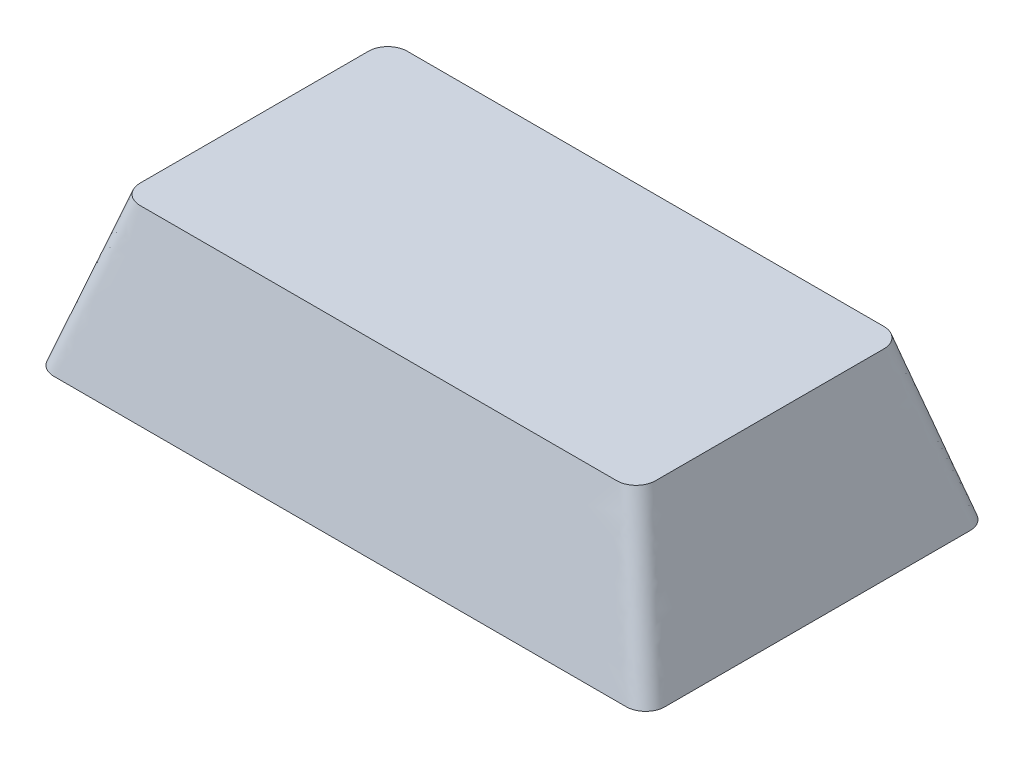
SolidWorks part; units mm, degrees
ref_plane "Alzado" through (0, 0, 0) normal (0, 0, 1) x (1, 0, 0)
ref_plane "Planta" through (0, 0, 0) normal (0, 1, 0) x (1, 0, 0)
ref_plane "Vista lateral" through (0, 0, 0) normal (1, 0, 0) x (0, 0, -1)
sketch "Croquis2" plane through (0, 0, 0) normal (0, 1, 0) x (1, 0, 0)
  line L1 (-14.986, -9.0043) -> (14.986, -9.0043)
  line L2 (-16.002, -7.9883) -> (-16.002, 7.9883)
  line L3 (-14.986, 9.0043) -> (14.986, 9.0043)
  line L4 (16.002, -7.9883) -> (16.002, 7.9883)
  arc A0 (-16.002, 7.9883) -> (-14.986, 9.0043) centre (-14.986, 7.9883) cw
  arc A1 (-14.986, -9.0043) -> (-16.002, -7.9883) centre (-14.986, -7.9883) cw
  arc A2 (14.986, -9.0043) -> (16.002, -7.9883) centre (14.986, -7.9883) ccw
  arc A3 (14.986, 9.0043) -> (16.002, 7.9883) centre (14.986, 7.9883) cw
  point P4 (16.002, 0)
  point P6 (0, 9.0043)
  dimension "D3" = 1.016
  dimension "D1" = 32.004
  dimension "D2" = 18.0086
ref_plane "Plano1" through (0, 8.001, 0) normal (0, 1, 0) x (1, 0, 0)
sketch "Croquis3" plane through (0, 8.001, 0) normal (0, 1, 0) x (1, 0, 0)
  line L1 (-12.4841, -6.9977) -> (12.4841, -6.9977)
  line L2 (-13.5001, -5.9817) -> (-13.5001, 5.9817)
  line L3 (-12.4841, 6.9977) -> (12.4841, 6.9977)
  line L4 (13.5001, -5.9817) -> (13.5001, 5.9817)
  line L5 (-13.5001, -6.9977) -> (13.5001, 6.9977) construction
  line L6 (-13.5001, 6.9977) -> (13.5001, -6.9977) construction
  arc A0 (12.4841, 6.9977) -> (13.5001, 5.9817) centre (12.4841, 5.9817) cw
  arc A1 (12.4841, -6.9977) -> (13.5001, -5.9817) centre (12.4841, -5.9817) ccw
  arc A2 (-12.4841, -6.9977) -> (-13.5001, -5.9817) centre (-12.4841, -5.9817) cw
  arc A3 (-13.5001, 5.9817) -> (-12.4841, 6.9977) centre (-12.4841, 5.9817) cw
  point P0 (0, 0)
  dimension "D3" = 1.016
  dimension "D1" = 27.0002
  dimension "D2" = 13.9954
loft "Recubrir1" add profiles "Croquis3", "Croquis2"
